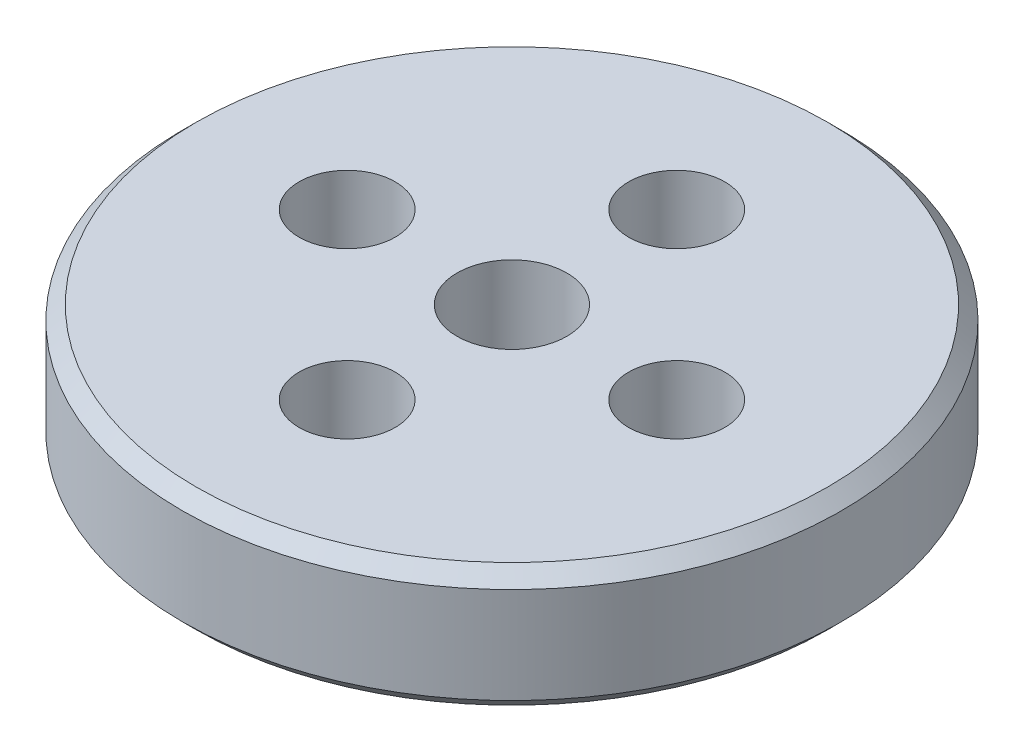
SolidWorks part; units mm, degrees
ref_plane "Front Plane" through (0, 0, 0) normal (0, 0, 1) x (1, 0, 0)
ref_plane "Top Plane" through (0, 0, 0) normal (0, 1, 0) x (1, 0, 0)
ref_plane "Right Plane" through (0, 0, 0) normal (1, 0, 0) x (0, 0, -1)
sketch "Sketch2" plane through (0, 0, 0) normal (0, 1, 0) x (1, 0, 0)
  circle A0 centre (0, 0) radius 16
  circle A1 centre (0, 0) radius 18
  circle A2 centre (0, 0) radius 24
  circle A4 centre (0, 0) radius 4
  circle A5 centre (0, 12) radius 3.5
  circle A6 centre (12, 0) radius 3.5
  circle A7 centre (0, -12) radius 3.5
  circle A8 centre (-12, 0) radius 3.5
  point P18 (0, 0)
  dimension "D1" = 48
  dimension "D2" = 36
  dimension "D3" = 32
  dimension "D4" = 7
  dimension "D5" = 8
  dimension "D7" = 4
extrude "Boss-Extrude2" add sketch "Sketch2" along normal blind 9 contours A2 A1 region at (-23.3212, 0, 0)
extrude "Boss-Extrude3" add sketch "Sketch2<3>" along normal blind 7 from offset 2 contours A1 A0 | A0 A8 A7 A6 A5 A4 region at (-15.5475, 0, 0) region at (-17.4909, 0, 0)
sketch "Sketch2<3>" plane through (0, 0, 0) normal (0, 1, 0) x (1, 0, 0) same geometry as "Sketch2"
chamfer "Chamfer1" distance 1 angle 45 2 edges at (0, 0, 24) (0, 9, 24)
chamfer "Chamfer2" distance 2 angle 45 1 edges at (0, 2, 18)
